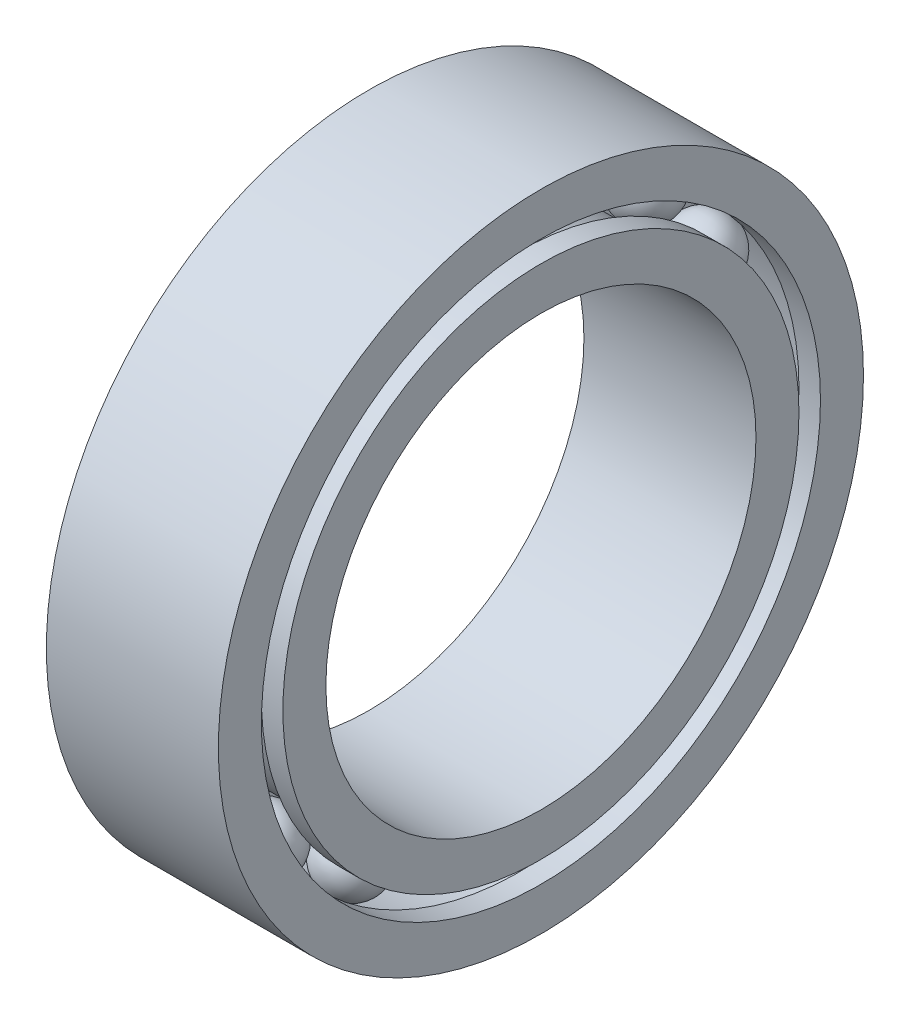
SolidWorks part; units mm, degrees
material "铸造合金钢"
ref_plane "前视基准面" through (0, 0, 0) normal (0, 0, 1) x (1, 0, 0)
ref_plane "上视基准面" through (0, 0, 0) normal (0, 1, 0) x (1, 0, 0)
ref_plane "右视基准面" through (0, 0, 0) normal (1, 0, 0) x (0, 0, -1)
sketch "草图1" plane through (0, 0, 0) normal (1, 0, 0) x (0, 0, -1)
  line L0 (0, 7) -> (0, 5.5)
  line L1 (2.6788, 6.4672) -> (2.1048, 5.0813)
  line L2 (4.9497, 4.9497) -> (3.8891, 3.8891)
  line L3 (6.4672, 2.6788) -> (5.0813, 2.1048)
  line L4 (7, 0) -> (5.5, 0)
  line L5 (6.4672, -2.6788) -> (5.0813, -2.1048)
  line L6 (4.9497, -4.9497) -> (3.8891, -3.8891)
  line L7 (2.6788, -6.4672) -> (2.1048, -5.0813)
  line L8 (0, -7) -> (0, -5.5)
  line L9 (-2.6788, -6.4672) -> (-2.1048, -5.0813)
  line L10 (-4.9497, -4.9497) -> (-3.8891, -3.8891)
  line L11 (-6.4672, -2.6788) -> (-5.0813, -2.1048)
  line L12 (-7, 0) -> (-5.5, 0)
  line L13 (-6.4672, 2.6788) -> (-5.0813, 2.1048)
  line L14 (-4.9497, 4.9497) -> (-3.8891, 3.8891)
  line L15 (-2.6788, 6.4672) -> (-2.1048, 5.0813)
  circle A0 centre (0, 0) radius 5
  circle A1 centre (0, 0) radius 5.5
  circle A2 centre (0, 0) radius 7
  circle A3 centre (0, 0) radius 7.5
  circle A4 centre (0, 6.25) radius 0.75
  circle A5 centre (2.3918, 5.7742) radius 0.75
  circle A6 centre (4.4194, 4.4194) radius 0.75
  circle A7 centre (5.7742, 2.3918) radius 0.75
  circle A8 centre (6.25, 0) radius 0.75
  circle A9 centre (5.7742, -2.3918) radius 0.75
  circle A10 centre (4.4194, -4.4194) radius 0.75
  circle A11 centre (2.3918, -5.7742) radius 0.75
  circle A12 centre (0, -6.25) radius 0.75
  circle A13 centre (-2.3918, -5.7742) radius 0.75
  circle A14 centre (-4.4194, -4.4194) radius 0.75
  circle A15 centre (-5.7742, -2.3918) radius 0.75
  circle A16 centre (-6.25, 0) radius 0.75
  circle A17 centre (-5.7742, 2.3918) radius 0.75
  circle A18 centre (-4.4194, 4.4194) radius 0.75
  circle A19 centre (-2.3918, 5.7742) radius 0.75
  circle A20 centre (0, 0) radius 6.25
  point P42 (0, 0)
  point P74 (0, 0)
  dimension "D1" = 10
  dimension "D2" = 11
  dimension "D3" = 14
  dimension "D4" = 15
  dimension "D5" = 16
  dimension "D6" = 16
revolve "旋转1" add sketch "草图1" angle 360 about L0 region at (0, 6.5601, -0.3244) region at (0, 5.9237, -0.3119)
extrude "凸台-拉伸1" add sketch "草图1<4>" along normal blind 2 and the other way blind 2 separate body contours A1 A0 | A3 A2 region at (0, 5.2417, -1.0426) region at (0, 0, 7.2879)
sketch "草图1<4>" plane through (0, 0, 0) normal (1, 0, 0) x (0, 0, -1) same geometry as "草图1"
pattern_circular "阵列(圆周)6" count 16 over 360 about axis through (2, 0, 0) along (1, 0, 0) of bodies 106
sketch "草图2" plane through (-2, 0, 0) normal (-1, 0, 0) x (0, 0, 1)
  circle A0 centre (0, 0) radius 5.5
  circle A1 centre (0, 0) radius 6
  circle A2 centre (0, 0) radius 7
  circle A3 centre (0, 0) radius 6.5
  circle M2 centre (0, 0) radius 5.5
  dimension "D1" = 12
  dimension "D2" = 13
extrude "凸台-拉伸2" add sketch "草图2" against normal blind 0.5 contours A1 M2 | A2 A3 region at (-2, 0, -5.8303) region at (-2, 0, -6.802)
sketch "草图3" plane through (2, 0, 0) normal (1, 0, 0) x (0, 0, -1)
  circle A0 centre (0, 0) radius 5.5 construction
  circle A1 centre (0, 0) radius 5.5
  circle A2 centre (0, 0) radius 6 construction
  circle A3 centre (0, 0) radius 6
  circle A4 centre (0, 0) radius 6.5 construction
  circle A5 centre (0, 0) radius 6.5
  circle A6 centre (0, 0) radius 7 construction
  circle A7 centre (0, 0) radius 7
  circle M2 centre (0, 0) radius 5.5
extrude "凸台-拉伸3" add sketch "草图3" against normal blind 0.5 contours A3 M2 | A7 A5 region at (2, 0, 5.8303) region at (2, 0, 6.802)
